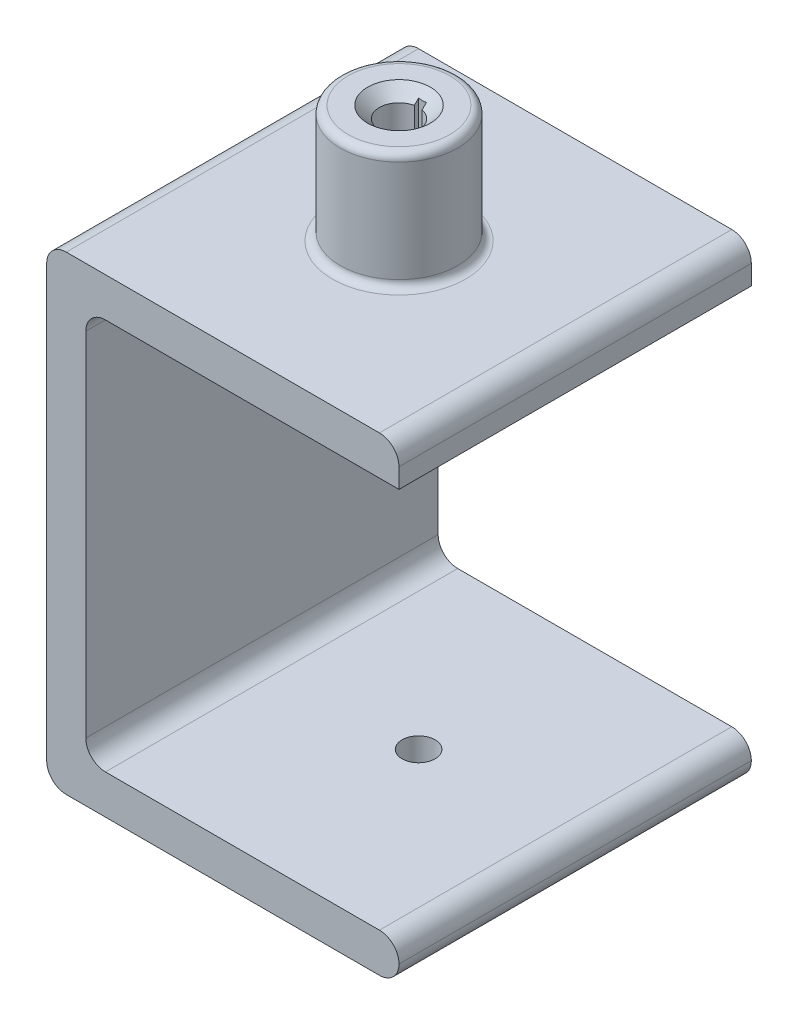
SolidWorks part; units mm, degrees
material "6061 Alloy"
ref_plane "Front Plane" through (0, 0, 0) normal (0, 0, 1) x (1, 0, 0)
ref_plane "Top Plane" through (0, 0, 0) normal (0, 1, 0) x (1, 0, 0)
ref_plane "Right Plane" through (0, 0, 0) normal (1, 0, 0) x (0, 0, -1)
sketch "Sketch1" plane through (0, 0, 0) normal (0, 0, 1) x (1, 0, 0)
  line L0 (0, 0) -> (0, 152.4)
  line L1 (0, 0) -> (114.3, 0)
  line L2 (0, 152.4) -> (114.3, 152.4)
  line L3 (114.3, 152.4) -> (114.3, 139.7)
  line L4 (114.3, 139.7) -> (12.7, 139.7)
  line L5 (12.7, 139.7) -> (12.7, 12.7)
  line L6 (12.7, 12.7) -> (114.3, 12.7)
  line L7 (114.3, 12.7) -> (114.3, 0)
  line L8 (12.7, 76.2) -> (0, 76.2) construction
  dimension "D1" = 12.7
  dimension "D2" = 114.3
  dimension "D3" = 152.4
extrude "Boss-Extrude1" add sketch "Sketch1" along normal mid plane 114.3
fillet "Fillet1" radius 6.35 2 edges at (12.7, 12.7, 0) (12.7, 139.7, 0)
fillet "Fillet2" radius 6.35 2 edges at (0, 0, 0) (0, 152.4, 0)
fillet "Fillet3" radius 6.35 3 edges at (114.3, 0, 0) (114.3, 12.7, 0) (114.3, 152.4, 0)
hole_wizard "1/2-13 Tapped Hole1" positions "Sketch5" profile "Sketch6" tap size "1/2-13" standard "ANSI Inch" end condition up to next
sketch "Sketch5" plane through (0, 0, 0) normal (0, -1, 0) x (-1, 0, 0)
  line L4 (0, 0) -> (-63.5, 0)
  point P0 (-63.5, 0)
  dimension "D1" = 63.5
sketch "Sketch6" plane through (63.5, 0, 0) normal (1, 0, 0) x (0, 0, -1)
  line L0 (0, 0) -> (0, 12.7)
  line L1 (0, 12.7) -> (5.3581, 12.7)
  line L2 (5.3581, 12.7) -> (5.3581, 0)
  line L5 (5.3581, 0) -> (0, 0)
  line L11 (0, -6.35) -> (0, 107.95) construction
  dimension "Thru Tap Drill Dia." = 10.7163
  dimension "Thru Tap Drill Depth" = 12.7
cosmetic thread "Hole Thread1" parameters "D2"=12.7
sketch "Sketch7" plane through (0, 152.4, 0) normal (0, 1, 0) x (1, 0, 0)
  line L0 (107.95, -57.15) -> (6.35, -57.15) construction
  line L1 (57.15, 0) -> (57.15, 6.35) construction
  line L2 (58.42, 6.2217) -> (58.42, 7.62)
  line L3 (58.42, 7.62) -> (55.88, 7.62)
  line L4 (55.88, 7.62) -> (55.88, 6.2217)
  circle A0 centre (57.15, 0) radius 19.05
  arc A1 (55.88, 6.2217) -> (58.42, 6.2217) centre (57.15, 0) ccw
  point P5 (57.15, -57.15)
  point P11 (57.15, 7.62)
  dimension "D1" = 38.1
  dimension "D2" = 12.7
  dimension "D3" = 7.62
  dimension "D4" = 2.54
extrude "Boss-Extrude2" add sketch "Sketch7" along normal blind 38.1
sketch "Sketch8" plane through (0, 152.4, 0) normal (0, 1, 0) x (1, 0, 0)
  circle A0 centre (57.15, 0) radius 8.382
  dimension "D1" = 16.764
extrude "Cut-Extrude1" cut sketch "Sketch8" along normal blind 1.524
fillet "Fillet4" radius 2.54 2 edges at (76.2, 152.4, 0) (38.1, 190.5, 0)
chamfer "Chamfer1" distance 3.81 angle 45 1 edges at (57.15, 190.5, 6.35)
